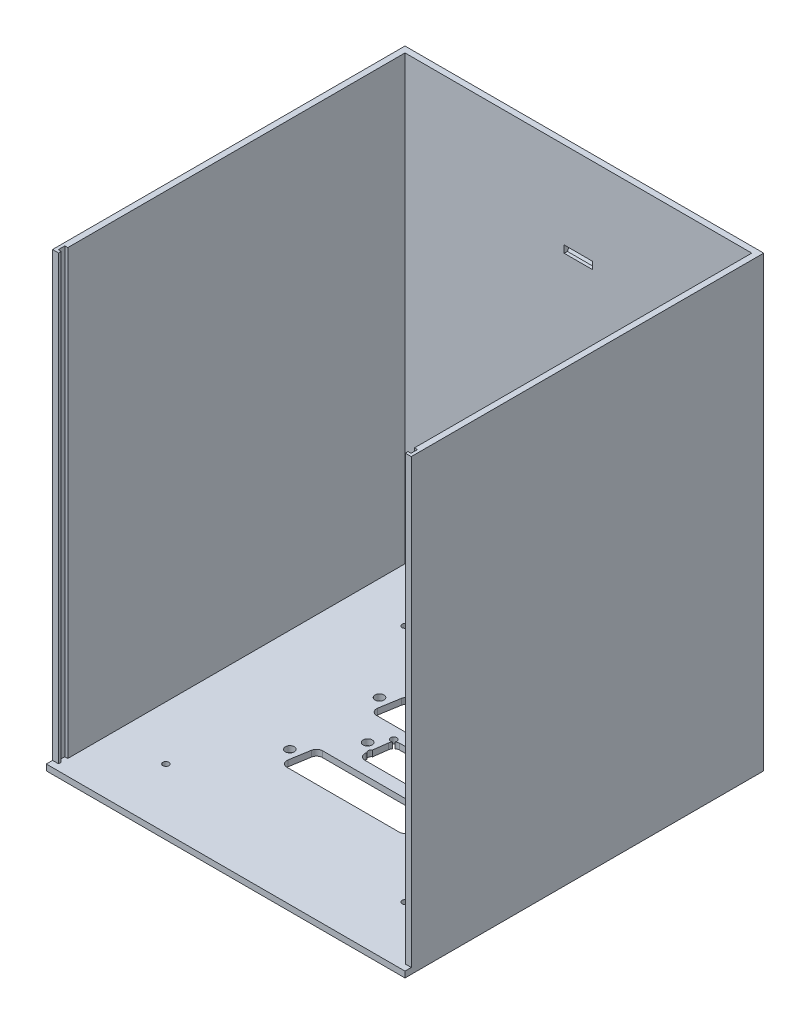
SolidWorks part; units mm, degrees
other "Markup1"
sketch "Sketch8" plane through (60, 0, -60) normal (0.7052, -0.7014, -0.1039) x (0.274, 0.4048, -0.8724)
other "Markup2"
sketch "Sketch9" plane through (60, 0, -60) normal (0.9922, -0.0018, -0.1244) x (-0.0942, 0.6423, -0.7606)
ref_plane "Front Plane" through (0, 0, 0) normal (0, 0, 1) x (1, 0, 0)
ref_plane "Top Plane" through (0, 0, 0) normal (0, 1, 0) x (1, 0, 0)
ref_plane "Right Plane" through (0, 0, 0) normal (1, 0, 0) x (0, 0, -1)
sketch "Sketch1" plane through (0, 0, 0) normal (0, 1, 0) x (1, 0, 0)
  line L5 (-60, 60) -> (60, 60)
  line L6 (-60, 60) -> (-60, -60)
  line L7 (-60, -60) -> (60, -60)
  line L8 (60, 60) -> (60, -60)
  dimension "D1" = 120
  dimension "D2" = 120
  dimension "D3" = 60
  dimension "D4" = 60
extrude "Main-Body" add sketch "Sketch1" along normal blind 150
sketch "Sketch11" plane through (0, 150, 0) normal (0, 1, 0) x (1, 0, 0)
  line L0 (-60, 60) -> (-60, -60) construction
  line L1 (58, -60) -> (-58, -60)
  line L2 (58, -60) -> (58, 58)
  line L3 (58, 58) -> (-58, 58)
  line L4 (-58, -60) -> (-58, 58)
  line L5 (58, -60) -> (-58, 58) construction
  line L6 (58, 58) -> (-58, -60) construction
  line L13 (60, 60) -> (-60, 60) construction
  point P0 (0, -1)
  dimension "D1" = 116
  dimension "D2" = 118
  dimension "D6" = 2
  dimension "D7" = 2
extrude "Hollow" cut sketch "Sketch11" against normal blind 148
sketch "Sketch12" plane through (0, 150, 0) normal (0, 1, 0) x (1, 0, 0)
  line L0 (-60, 60) -> (-60, -60) construction
  line L1 (-58, -60) -> (-60, -60)
  line L2 (-58, -60) -> (-58, -57.9)
  line L3 (-58, -57.9) -> (-60, -57.9)
  line L4 (-60, -60) -> (-60, -57.9)
  dimension "D1" = 2.1
extrude "Lid-Cut" cut sketch "Sketch12" against normal blind 148
mirror "Mirror-Lid-Cut" about plane through (0, 0, 0) normal (1, 0, 0) of "Lid-Cut"
sketch "Sketch13" plane through (0, 150, 0) normal (0, 1, 0) x (1, 0, 0)
  line L0 (-58, 58) -> (-58, -57.9) construction
  line L1 (-58, -57) -> (-59, -57)
  line L2 (-58, -57) -> (-58, -54.8)
  line L3 (-58, -54.8) -> (-59, -54.8)
  line L4 (-59, -57) -> (-59, -54.8)
  line L5 (-58, -57.9) -> (-60, -57.9) construction
  dimension "D1" = 1
  dimension "D2" = 0.9
  dimension "D3" = 2.2
extrude "Rail-Cut" cut sketch "Sketch13" against normal blind 148
mirror "Mirror-Rail-Cut" about plane through (0, 0, 0) normal (1, 0, 0) of "Rail-Cut"
sketch "Sketch2" plane through (0, 0, 0) normal (0, -1, 0) x (1, 0, 0)
  circle A0 centre (-40, 40) radius 1
  circle A1 centre (40, 40) radius 1
  circle A2 centre (40, -40) radius 1
  circle A3 centre (-40, -40) radius 1
  dimension "D1" = 40
  dimension "D3" = 2
  dimension "D2" = 40
  dimension "D4" = 2
  dimension "D5" = 2
extrude "Main-PCB-Holes" cut sketch "Sketch2" against normal up to next
sketch "Sketch3" plane through (0, 150, 0) normal (0, 1, 0) x (1, 0, 0)
  line L0 (-9, 5.23) -> (9, 5.23) construction
  circle A0 centre (-9, 5.23) radius 1.05
  circle A1 centre (9, 5.23) radius 1.05
  circle A2 centre (9, -2.27) radius 1.05
  circle A3 centre (-9, -2.27) radius 1.05
  dimension "D1" = 9
  dimension "D3" = 2.1
  dimension "D2" = 5.23
  dimension "D4" = 2
  dimension "D6" = 18
  dimension "D7" = 7.5
  dimension "D5" = 2
extrude "LED-PCB-Holes" cut sketch "Sketch3" against normal up to next
sketch "Sketch4" plane through (0, 0, 0) normal (0, -1, 0) x (1, 0, 0)
  line L0 (-12.5, 0) -> (12.5, 0) construction
  line L1 (-23.52, -15) -> (23.52, -15) construction
  line L2 (-6.8916, -5.1179) -> (6.8916, -5.1179)
  line L4 (-7.7666, 5.6321) -> (7.7666, 5.6321)
  line L6 (-17.6522, -20.0462) -> (17.6522, -20.0462)
  line L8 (-18.7772, -9.2962) -> (18.7772, -9.2962)
  line L10 (-23.52, 15) -> (23.52, 15) construction
  line L11 (-17.6522, 9.9538) -> (17.6522, 9.9538)
  line L13 (-18.7772, 20.7038) -> (18.7772, 20.7038)
  line L16 (-19.625, 11.625) -> (-20.75, 18.375)
  line L19 (20.75, 18.375) -> (19.625, 11.625)
  line L22 (-8.875, -3.375) -> (-9.75, 3.375)
  line L25 (9.75, 3.375) -> (8.875, -3.375)
  line L28 (-20.75, -11.625) -> (-19.625, -18.375)
  line L31 (19.625, -18.375) -> (20.75, -11.625)
  circle A0 centre (-12.5, 0) radius 1.5
  circle A1 centre (12.5, 0) radius 1.5
  circle A2 centre (-23.52, -15) radius 1.5
  circle A3 centre (23.52, -15) radius 1.5
  circle A4 centre (-23.52, 15) radius 1.5
  circle A5 centre (23.52, 15) radius 1.5
  arc A6 (18.7772, 20.7038) -> (20.75, 18.375) centre (18.7772, 18.7038) cw
  arc A7 (-18.7772, 20.7038) -> (-20.75, 18.375) centre (-18.7772, 18.7038) ccw
  arc A8 (17.6522, 9.9538) -> (19.625, 11.625) centre (17.6522, 11.9538) ccw
  arc A9 (-17.6522, 9.9538) -> (-19.625, 11.625) centre (-17.6522, 11.9538) cw
  arc A10 (20.75, -11.625) -> (18.7772, -9.2962) centre (18.7772, -11.2962) ccw
  arc A11 (17.6522, -20.0462) -> (19.625, -18.375) centre (17.6522, -18.0462) ccw
  arc A12 (-19.625, -18.375) -> (-17.6522, -20.0462) centre (-17.6522, -18.0462) ccw
  arc A13 (-20.75, -11.625) -> (-18.7772, -9.2962) centre (-18.7772, -11.2962) cw
  arc A14 (7.7666, 5.6321) -> (9.75, 3.375) centre (7.7666, 3.6321) cw
  arc A15 (8.875, -3.375) -> (6.8916, -5.1179) centre (6.8916, -3.1179) cw
  arc A16 (-8.875, -3.375) -> (-6.8916, -5.1179) centre (-6.8916, -3.1179) ccw
  arc A17 (-9.75, 3.375) -> (-7.7666, 5.6321) centre (-7.7666, 3.6321) cw
  point P4 (0, 0)
  point P12 (0, 5.6321)
  point P17 (0, -15)
  point P24 (0, -20.0462)
  point P29 (0, 15)
  point P32 (0, -5.1179)
  point P34 (0, 9.9538)
  point P35 (0, 20.7038)
  point P36 (0, -9.2962)
  point P38 (20.1875, -15)
  point P41 (9.3125, 0)
  point P42 (20.1875, 15)
  point P52 (21.1381, 20.7038)
  point P59 (19.3465, 9.9538)
  point P66 (21.1381, -9.2962)
  point P69 (19.3465, -20.0462)
  point P76 (10.0426, 5.6321)
  point P79 (8.6491, -5.1179)
  dimension "D1" = 3
  dimension "D2" = 3
  dimension "D8" = 3
  dimension "D7" = 3
  dimension "D14" = 3
  dimension "D15" = 3
  dimension "D4" = 41.5
  dimension "D21" = 2
  dimension "D25" = 2
  dimension "D27" = 2
  dimension "D3" = 25
  dimension "D6" = 10.75
  dimension "D9" = 47.04
  dimension "D13" = 15
  dimension "D16" = 47.04
  dimension "D18" = 10.75
  dimension "D19" = 15
  dimension "D20" = 10.75
  dimension "D28" = 39.25
  dimension "D30" = 41.5
  dimension "D31" = 39.25
  dimension "D32" = 19.5
  dimension "D33" = 17.75
extrude "Connector-Slots" cut sketch "Sketch4" against normal up to next
sketch "Sketch14" plane through (0, 0, 0) normal (1, 0, 0) x (0, 0, -1)
  line L0 (58, 121) -> (60, 121)
  line L1 (58, 2) -> (58, 150) construction
  line L2 (60, 150) -> (60, 0) construction
  line L3 (60, 121) -> (60, 120.88)
  line L4 (60, 120.88) -> (60, 119.88)
  line L5 (60, 119.88) -> (59.8206, 119.88)
  line L6 (59.8206, 119.88) -> (59.07, 118.58)
  line L7 (59.07, 118.58) -> (58, 118.58)
  line L10 (60, 150) -> (-57.9, 150) construction
  line L11 (58, 121) -> (58, 118.58)
  dimension "D1" = 29
  dimension "D2" = 0.12
  dimension "D3" = 2.42
  dimension "D4" = 1
  dimension "D5" = 30
  dimension "D6" = 1.07
extrude "Cut-Extrude1" cut sketch "Sketch14" against normal mid plane 9.5
